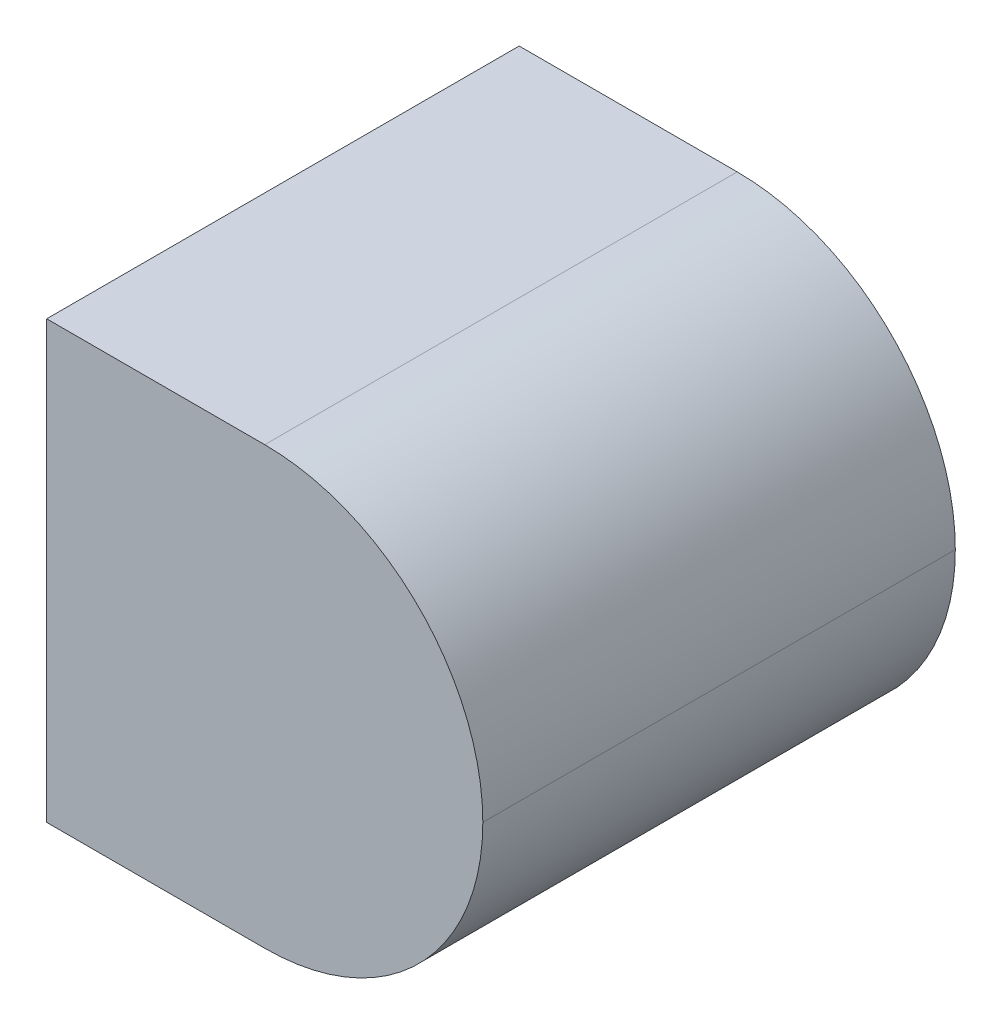
SolidWorks part; units mm, degrees
ref_plane "XY" through (0, 0, 0) normal (0, 0, 1) x (1, 0, 0)
ref_plane "XZ" through (0, 0, 0) normal (0, 1, 0) x (1, 0, 0)
ref_plane "YZ" through (0, 0, 0) normal (1, 0, 0) x (0, 0, -1)
sketch "Sketch1" plane through (0, 0, 0) normal (0, 0, 1) x (1, 0, 0)
  line L1 (3, 3) -> (-3, 3)
  line L2 (3, 3) -> (3, -3)
  line L3 (3, -3) -> (-3, -3)
  line L4 (-3, 3) -> (-3, -3)
  line L5 (3, 3) -> (-3, -3) construction
  line L6 (3, -3) -> (-3, 3) construction
  point P0 (0, 0)
  dimension "D1" = 6
  dimension "D2" = 6
extrude "Boss-Extrude1" add sketch "Sketch1" along normal blind 6.5
fillet "Fillet1" radius 3 2 edges at (3, -3, 3.25) (3, 3, 3.25)
sketch "Sketch2" plane through (-3, 0, 0) normal (-1, 0, 0) x (0, 0, 1)
  line L0 (0, 3) -> (0, -3) construction
  line L1 (6.5, 3) -> (0, 3) construction
  circle A0 centre (3.25, 0) radius 1.6
  point P4 (0, 0)
  point P7 (3.25, 3)
  dimension "D1" = 3.2
extrude "Cut-Extrude1" cut sketch "Sketch2" against normal blind 2
